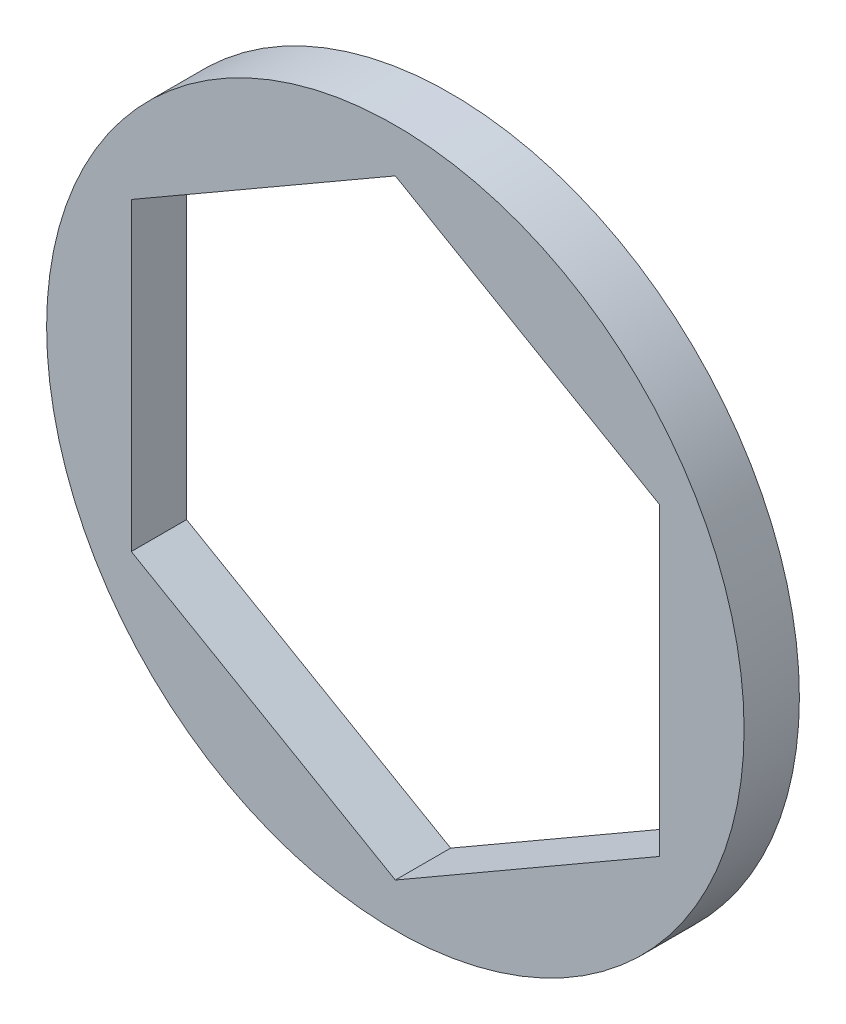
SolidWorks part; units mm, degrees
material "Nylon 101"
ref_plane "Front Plane" through (0, 0, 0) normal (0, 0, 1) x (1, 0, 0)
ref_plane "Top Plane" through (0, 0, 0) normal (0, 1, 0) x (1, 0, 0)
ref_plane "Right Plane" through (0, 0, 0) normal (1, 0, 0) x (0, 0, -1)
sketch "Sketch1" plane through (0, 0, 0) normal (0, 0, 1) x (1, 0, 0)
  line L1 (6.731, 3.8861) -> (0, 7.7723)
  line L2 (0, 7.7723) -> (-6.731, 3.8861)
  line L3 (-6.731, 3.8861) -> (-6.731, -3.8861)
  line L4 (-6.731, -3.8861) -> (0, -7.7723)
  line L5 (0, -7.7723) -> (6.731, -3.8861)
  line L6 (6.731, -3.8861) -> (6.731, 3.8861)
  circle A0 centre (0, 0) radius 6.731 construction
  circle A1 centre (0, 0) radius 8.89
  dimension "D1" = 13.462
  dimension "D2" = 17.78
extrude "Boss-Extrude1" add sketch "Sketch1" along normal blind 1.4097
